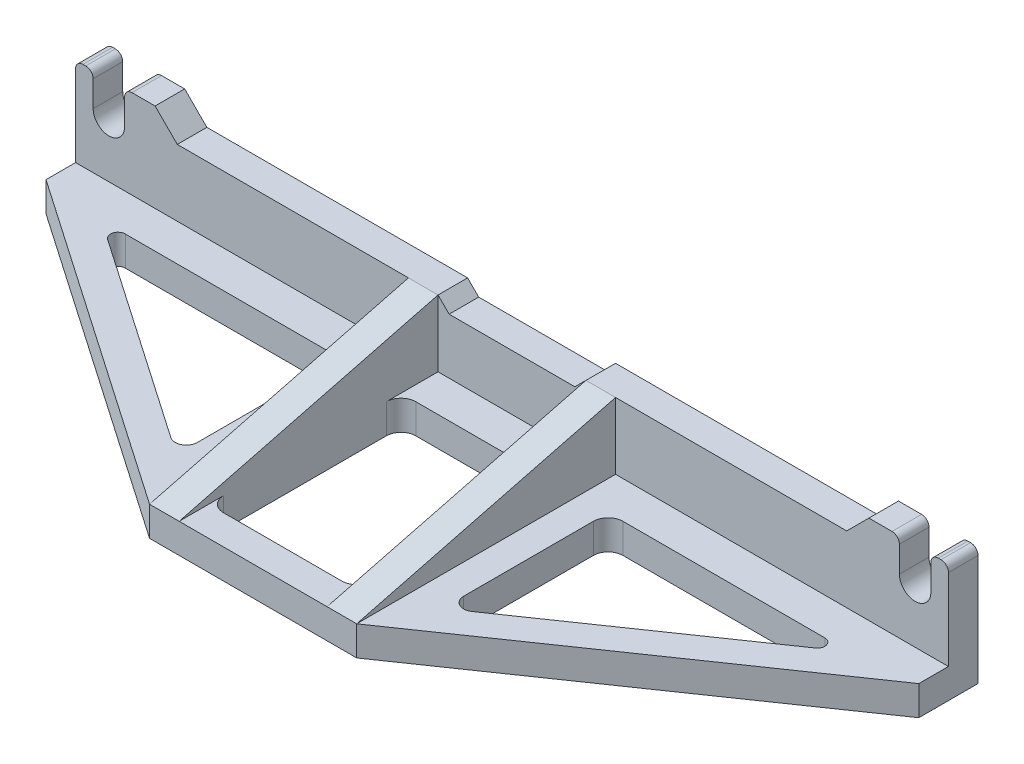
SolidWorks part; units mm, degrees
ref_plane "Front Plane" through (0, 0, 0) normal (0, 0, 1) x (1, 0, 0)
ref_plane "Top Plane" through (0, 0, 0) normal (0, 1, 0) x (1, 0, 0)
ref_plane "Right Plane" through (0, 0, 0) normal (1, 0, 0) x (0, 0, -1)
sketch "Sketch1" plane through (0, 0, 0) normal (0, 0, 1) x (1, 0, 0)
  line L0 (4.25, 0) -> (4.25, 9)
  line L1 (4.25, 9) -> (9, 9)
  line L2 (9, 9) -> (9, -23)
  line L3 (9, -23) -> (-227, -23)
  line L4 (-227, -23) -> (-227, 9)
  line L5 (-213.75, 9) -> (-4.25, 9)
  line L6 (-4.25, 9) -> (-4.25, 0)
  line L7 (-4.25, 9) -> (4.25, 9) construction
  line L8 (-227, 9) -> (-222.25, 9)
  line L9 (-222.25, 9) -> (-222.25, 0)
  line L10 (-213.75, 0) -> (-213.75, 9)
  line L11 (-4.25, 0) -> (4.25, 0) construction
  line L12 (-222.25, 0) -> (-213.75, 0) construction
  line L13 (-213.75, 0) -> (-4.25, 0) construction
  line L14 (-205.5, 9) -> (-199.5, 3)
  line L15 (-199.5, 3) -> (-18.5, 3)
  line L16 (-18.5, 3) -> (-12.5, 9)
  line L17 (-109, 9) -> (-109, 43.7143) construction
  line L18 (-135, 9) -> (-126, 0)
  line L19 (-126, 0) -> (-92, 0)
  line L20 (-92, 0) -> (-83, 9)
  line L21 (-109, 0) -> (-109, 9) construction
  circle A0 centre (0, 0) radius 4.25
  circle A1 centre (-218, 0) radius 4.25
  point P28 (-109, 0)
  dimension "D1" = 8.5
  dimension "D4" = 218
  dimension "D2" = 8.25
  dimension "D3" = 18.75
  dimension "D5" = 236
  dimension "D6" = 8.25
  dimension "D7" = 32
  dimension "D8" = 135
  dimension "D9" = 135
  dimension "D10" = 26
  dimension "D11" = 26
extrude "Boss-Extrude1" add sketch "Sketch1" along normal blind 8 contours A1 L9 L8 L4 L3 L2 L1 L0 A0 L6 L5 L16 L15 L20 L19 L18 L14 L10 region at (-109, -9.8849, 0)
sketch "Sketch2" plane through (0, -23, 0) normal (0, -1, 0) x (1, 0, 0)
  line L0 (-227, 8) -> (-227, 16)
  line L1 (-227, 16) -> (-137, 78)
  line L2 (-137, 78) -> (-81, 78)
  line L3 (-81, 78) -> (9, 16)
  line L4 (9, 16) -> (9, 8)
  line L5 (9, 8) -> (-227, 8) construction
  line L6 (9, 8) -> (-227, 8)
  line L7 (-109, 8) -> (-109, 78) construction
  dimension "D1" = 8
  dimension "D2" = 56
  dimension "D3" = 70
extrude "Boss-Extrude2" add sketch "Sketch2" against normal blind 8
ref_plane "Plane1" through (-81, 0, 0) normal (1, 0, 0) x (0, 0, -1)
ref_plane "Plane2" through (-137, 0, 0) normal (1, 0, 0) x (0, 0, -1)
sketch "Sketch4" plane through (-81, 0, 0) normal (1, 0, 0) x (0, 0, -1)
  line L0 (-78, -15) -> (-8, 3)
  line L2 (-8, 0) -> (-8, -15)
  line L3 (-8, -15) -> (-78, -15)
  line L4 (-8, 0) -> (-8, 3) construction
  line L5 (-8, 0) -> (-8, 3)
extrude "Boss-Extrude3" add sketch "Sketch4" against normal blind 8
sketch "Sketch5" plane through (-137, 0, 0) normal (1, 0, 0) x (0, 0, -1)
  line L4 (-8, 3) -> (-78, -15)
  line L5 (-8, 0) -> (-8, 3)
  line L6 (-8, -15) -> (-8, 0)
  line L7 (-78, -15) -> (-8, -15)
  line L8 (-8, 3) -> (-78, -15)
  line L9 (-8, 0) -> (-8, 3)
  line L10 (-8, -15) -> (-8, 0)
  line L11 (-78, -15) -> (-8, -15)
  dimension "D1" = 0
extrude "Boss-Extrude4" add sketch "Sketch5" along normal blind 8
sketch "Sketch6" plane through (0, -15, 0) normal (0, 1, 0) x (1, 0, 0)
  line L0 (-129, -18) -> (-89, -18)
  line L1 (-129, -78) -> (-129, -8) construction
  line L2 (-89, -78) -> (-89, -8) construction
  line L3 (-89, -18) -> (-89, -70)
  line L4 (-89, -8) -> (-89, -78) construction
  line L5 (-89, -70) -> (-129, -70)
  line L6 (-129, -8) -> (-129, -78) construction
  line L7 (-129, -70) -> (-129, -18)
  line L8 (-89, -78) -> (-129, -78) construction
  line L9 (-129, -8) -> (-89, -8) construction
  dimension "D1" = 8
  dimension "D2" = 10
extrude "Cut-Extrude1" cut sketch "Sketch6" against normal through all
sketch "Sketch7" plane through (0, -15, 0) normal (0, 1, 0) x (1, 0, 0)
  line L0 (-73, -18) -> (-8.005, -18)
  line L1 (-8.005, -18) -> (-73, -62.7743)
  line L2 (-73, -62.7743) -> (-73, -18)
  line L3 (-145, -18) -> (-209.995, -18)
  line L4 (-209.995, -18) -> (-145, -62.7743)
  line L5 (-145, -62.7743) -> (-145, -18)
  line L6 (-137, -78) -> (-227, -16) construction
  line L7 (9, -16) -> (-81, -78) construction
  line L8 (-145, -18) -> (-129, -18) construction
  line L9 (-89, -18) -> (-73, -18) construction
  line L10 (-137, -78) -> (-137, -8) construction
  line L11 (-81, -78) -> (-81, -8) construction
  dimension "D1" = 8
  dimension "D2" = 8
  dimension "D3" = 8
  dimension "D4" = 8
extrude "Cut-Extrude2" cut sketch "Sketch7" against normal through all
fillet "Fillet1" radius 4 4 edges at (-73, -19, 18) (-129, -19, 18) (-89, -19, 18) (-145, -19, 18)
fillet "Fillet2" radius 2 2 edges at (-209.995, -19, 18) (-8.005, -19, 18)
fillet "Fillet3" radius 4 2 edges at (-129, -19, 70) (-89, -19, 70)
fillet "Fillet4" radius 3 2 edges at (-73, -19, 62.7743) (-145, -19, 62.7743)
fillet "Fillet5" radius 2 6 edges at (9, 9, 4) (4.25, 9, 4) (-4.25, 9, 4) (-213.75, 9, 4) (-222.25, 9, 4) (-227, 9, 4)
